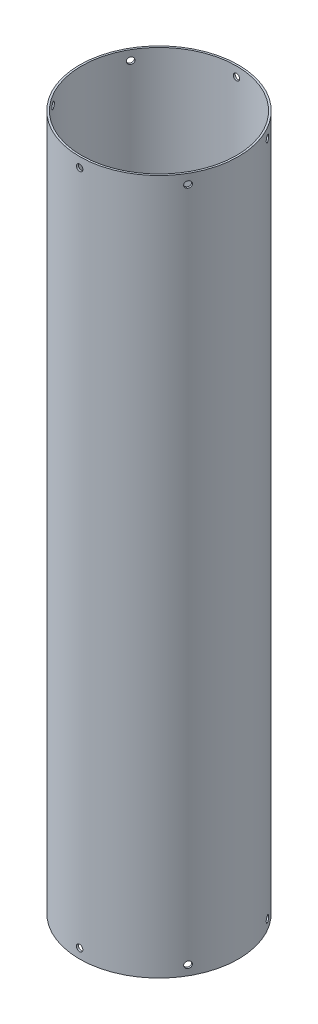
SolidWorks part; units mm, degrees
ref_plane "Front Plane" through (0, 0, 0) normal (0, 0, 1) x (1, 0, 0)
ref_plane "Top Plane" through (0, 0, 0) normal (0, 1, 0) x (1, 0, 0)
ref_plane "Right Plane" through (0, 0, 0) normal (1, 0, 0) x (0, 0, -1)
sketch "Sketch1" plane through (0, 0, 0) normal (0, 1, 0) x (1, 0, 0)
  circle A0 centre (0, 0) radius 78.359
  circle A1 centre (0, 0) radius 76.5175
  dimension "D1" = 156.718
  dimension "D2" = 153.035
extrude "Inner&OuterDiameter" add sketch "Sketch1" along normal blind 685.8
sketch "Sketch2" plane through (0, 0, 0) normal (0, 0, 1) x (1, 0, 0)
  line L0 (76.5175, 685.8) -> (-76.5175, 685.8) construction
  line L1 (-78.359, 0) -> (78.359, 0) construction
  circle A0 centre (0, 676.275) radius 3.175
  circle A1 centre (0, 9.525) radius 3.175
  dimension "D2" = 6.35
  dimension "D3" = 6.35
  dimension "D1" = 9.525
  dimension "D4" = 9.525
extrude "Top&BottomBoltHoles" cut sketch "Sketch2" against normal through all
pattern_circular "CirPattern1" count 6 over 360 about axis through (0, 685.8, 0) along (0, -1, 0) of "Top&BottomBoltHoles"
